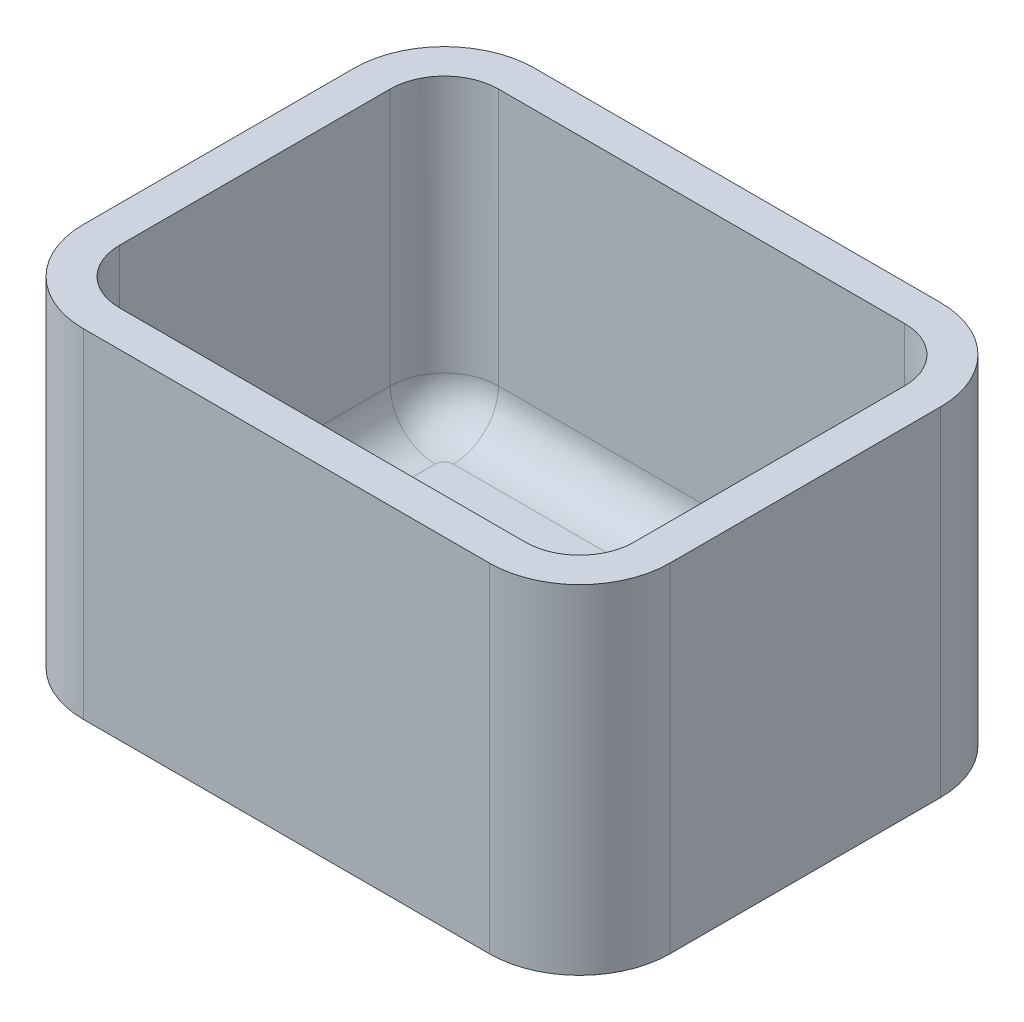
SolidWorks part; units mm, degrees
ref_plane "Plan de face" through (0, 0, 0) normal (0, 0, 1) x (1, 0, 0)
ref_plane "Plan de dessus" through (0, 0, 0) normal (0, 1, 0) x (1, 0, 0)
ref_plane "Plan de droite" through (0, 0, 0) normal (1, 0, 0) x (0, 0, -1)
sketch "Esquisse4" plane through (0, 0, 0) normal (0, 1, 0) x (1, 0, 0)
  line L1 (-52.2281, 66.2297) -> (77.7719, 66.2297)
  line L2 (-52.2281, 66.2297) -> (-52.2281, -33.7703)
  line L3 (-52.2281, -33.7703) -> (77.7719, -33.7703)
  line L4 (77.7719, 66.2297) -> (77.7719, -33.7703)
  dimension "D1" = 100
  dimension "D2" = 130
extrude "Boss.-Extru.4" add sketch "Esquisse4" along normal blind 75
ref_plane "Plan1" through (12.7719, 0, 0) normal (-1, 0, 0) x (0, 0, 1)
ref_plane "Plan2" through (0, 0, -16.2297) normal (0, 0, 1) x (1, 0, 0)
ref_axis "Axe1" through (12.7719, 110.2243, -16.2297) along (0, -1, 0)
fillet "Congé5" radius 20 4 edges at (77.7719, 37.5, 33.7703) (77.7719, 37.5, -66.2297) (-52.2281, 37.5, 33.7703) (-52.2281, 37.5, -66.2297)
sketch "Esquisse5" plane through (0, 75, 0) normal (0, 1, 0) x (1, 0, 0)
  line L24 (57.7719, 58.2297) -> (-32.2281, 58.2297)
  line L25 (69.7719, -13.7703) -> (69.7719, 46.2297)
  line L26 (-32.2281, -25.7703) -> (57.7719, -25.7703)
  line L27 (-44.2281, 46.2297) -> (-44.2281, -13.7703)
  line L28 (57.7719, 58.2297) -> (-32.2281, 58.2297)
  line L29 (69.7719, -13.7703) -> (69.7719, 46.2297)
  line L30 (-32.2281, -25.7703) -> (57.7719, -25.7703)
  line L31 (-44.2281, 46.2297) -> (-44.2281, -13.7703)
  arc A23 (69.7719, 46.2297) -> (57.7719, 58.2297) centre (57.7719, 46.2297) ccw
  arc A24 (57.7719, -25.7703) -> (69.7719, -13.7703) centre (57.7719, -13.7703) ccw
  arc A25 (-44.2281, -13.7703) -> (-32.2281, -25.7703) centre (-32.2281, -13.7703) ccw
  arc A26 (-32.2281, 58.2297) -> (-44.2281, 46.2297) centre (-32.2281, 46.2297) ccw
  arc A27 (69.7719, 46.2297) -> (57.7719, 58.2297) centre (57.7719, 46.2297) ccw
  arc A28 (57.7719, -25.7703) -> (69.7719, -13.7703) centre (57.7719, -13.7703) ccw
  arc A29 (-44.2281, -13.7703) -> (-32.2281, -25.7703) centre (-32.2281, -13.7703) ccw
  arc A30 (-32.2281, 58.2297) -> (-44.2281, 46.2297) centre (-32.2281, 46.2297) ccw
  dimension "D2" = 8
extrude "Enlèv. mat.-Extru.1" cut sketch "Esquisse5" against normal blind 67
fillet "Congé6" radius 10 8 edges at (66.2572, 8, -54.715) (69.7719, 8, -16.2297) (66.2572, 8, 22.2556) (12.7719, 8, 25.7703) (-40.7133, 8, 22.2556) (-44.2281, 8, -16.2297) (-40.7133, 8, -54.715) (12.7719, 8, -58.2297) type face fillet first side face at (12.7719, 41.5, 25.7703) first side face at (65.0146, 41.5, 21.0129) first side face at (69.7719, 41.5, -16.2297) first side face at (65.0146, 41.5, -53.4724) first side face at (-39.4707, 41.5, 21.0129) first side face at (-44.2281, 41.5, -16.2297) first side face at (-39.4707, 41.5, -53.4724) first side face at (12.7719, 41.5, -58.2297) second side face at (12.7719, 8, -16.2297) conic radius 10
